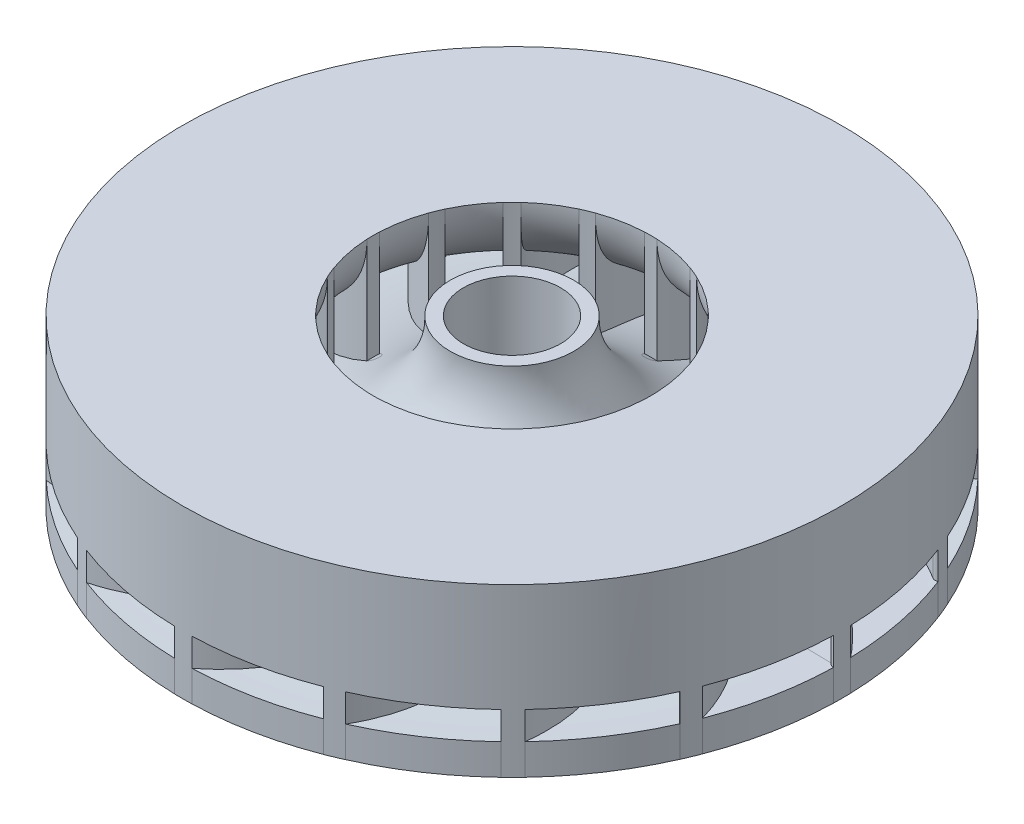
SolidWorks part; units mm, degrees
other "Markup1"
sketch "Sketch14" plane through (34.9924, 18.1689, 34.9924) normal (0.4024, 0.9092, 0.107) x (-0.9091, 0.4106, -0.0699)
material "AA356.0-F"
ref_plane "Front Plane" through (0, 0, 0) normal (0, 0, 1) x (1, 0, 0)
ref_plane "Top Plane" through (0, 0, 0) normal (0, 1, 0) x (1, 0, 0)
ref_plane "Right Plane" through (0, 0, 0) normal (1, 0, 0) x (0, 0, -1)
curve "Shroud Curve"
curve "Impeller Curve"
curve "Blade Curve"
sketch "Sketch2" plane through (0, 0, 0) normal (0, 0, 1) x (1, 0, 0)
  line L0 (14.2896, 17.1821) -> (33.9139, 17.1821)
  line L1 (33.9139, 17.1821) -> (33.9139, 6.0439)
  spline S0 degree 3 poles (-985.6672, 25.6238) (17.121, 24.6036) (14.2699, 20.8626) (14.29, 17.0771) (14.2924, 16.9214) (14.3025, 16.6646) (14.3304, 16.2921) (14.3832, 15.869) (14.4663, 15.4189) (14.5673, 15.0013) (14.692, 14.5874) (14.8412, 14.1777) (15.0158, 13.7731) (15.2158, 13.374) (15.4419, 12.981) (15.6996, 12.5875) (15.9902, 12.1947) (16.3155, 11.8043) (16.6762, 11.4178) (17.0667, 11.0427) (17.4864, 10.6798) (17.9347, 10.329) (18.4109, 9.9911) (18.9142, 9.6665) (19.4435, 9.3553) (20.0062, 9.0533) (20.6105, 8.7577) (21.2468, 8.4745) (21.9134, 8.2045) (22.6083, 7.9485) (23.3475, 7.7013) (24.1283, 7.4655) (24.9558, 7.241) (25.8242, 7.0305) (26.7261, 6.8369) (27.6431, 6.6639) (28.555, 6.5139) (29.435, 6.3888) (30.2578, 6.2886) (30.995, 6.2121) (31.6335, 6.1561) (32.1708, 6.1163) (32.6141, 6.0889) (32.9737, 6.0705) (33.2588, 6.0586) (33.476, 6.0514) (33.6399, 6.0473) (33.7596, 6.0451) (33.8432, 6.0441) (33.8894, 6.0439) (35.7046, 6.0419) (37.504, 6.9456) (38.7227, -993.9019) knots -0.448256 -0.448256 -0.448256 -0.448256 0.001273 0.002543 0.008858 0.020084 0.03357 0.053959 0.071547 0.088816 0.10582 0.123722 0.141437 0.159019 0.177608 0.196155 0.215799 0.236589 0.257482 0.279621 0.301942 0.324462 0.348334 0.372436 0.39676 0.422462 0.44954 0.477978 0.506547 0.536376 0.567388 0.600661 0.634851 0.670917 0.708547 0.746233 0.783584 0.820144 0.853551 0.883668 0.909634 0.93095 0.948727 0.963266 0.974429 0.983176 0.989512 0.994228 0.997631 0.999605 0.999804 1.216827 1.216827 1.216827 1.216827 only from (14.2896, 17.1821) to (33.9139, 6.0439) construction
  spline S1 degree 3 poles (14.2896, 17.1821) (14.2896, 17.1715) (14.2896, 17.1505) (14.29, 17.0771) (14.2924, 16.9214) (14.3025, 16.6646) (14.3304, 16.2921) (14.3832, 15.869) (14.4663, 15.4189) (14.5673, 15.0013) (14.692, 14.5874) (14.8412, 14.1777) (15.0158, 13.7731) (15.2158, 13.374) (15.4419, 12.981) (15.6996, 12.5875) (15.9902, 12.1947) (16.3155, 11.8043) (16.6762, 11.4178) (17.0667, 11.0427) (17.4864, 10.6798) (17.9347, 10.329) (18.4109, 9.9911) (18.9142, 9.6665) (19.4435, 9.3553) (20.0062, 9.0533) (20.6105, 8.7577) (21.2468, 8.4745) (21.9134, 8.2045) (22.6083, 7.9485) (23.3475, 7.7013) (24.1283, 7.4655) (24.9558, 7.241) (25.8242, 7.0305) (26.7261, 6.8369) (27.6431, 6.6639) (28.555, 6.5139) (29.435, 6.3888) (30.2578, 6.2886) (30.995, 6.2121) (31.6335, 6.1561) (32.1708, 6.1163) (32.6141, 6.0889) (32.9737, 6.0705) (33.2588, 6.0586) (33.476, 6.0514) (33.6399, 6.0473) (33.7596, 6.0451) (33.8432, 6.0441) (33.8894, 6.0439) (33.909, 6.0439) (33.9123, 6.0439) (33.9139, 6.0439) knots 0 0 0 0 0.001273 0.002543 0.008858 0.020084 0.03357 0.053959 0.071547 0.088816 0.10582 0.123722 0.141437 0.159019 0.177608 0.196155 0.215799 0.236589 0.257482 0.279621 0.301942 0.324462 0.348334 0.372436 0.39676 0.422462 0.44954 0.477978 0.506547 0.536376 0.567388 0.600661 0.634851 0.670917 0.708547 0.746233 0.783584 0.820144 0.853551 0.883668 0.909634 0.93095 0.948727 0.963266 0.974429 0.983176 0.989512 0.994228 0.997631 0.999605 0.999804 1 1 1 1
ref_axis "Axis1" through (0, 16.8793, 0) along (0, -1, 0)
revolve "Shroud" add sketch "Sketch2" angle 360 about axis through (0, 16.8793, 0) along (0, -1, 0)
sketch "Sketch3" plane through (0, 0, 0) normal (0, 0, 1) x (1, 0, 0)
  line L0 (33.9128, 3.175) -> (33.9128, 0)
  line L1 (33.9128, 0) -> (0, 0)
  line L2 (0, 0) -> (0, 17.1821)
  line L3 (33.9139, 17.1821) -> (-33.9139, 17.1821) construction
  line L4 (6.35, 17.1685) -> (0, 17.1821)
  spline S7 degree 3 poles (-1991.3665, 109.7009) (15.6852, 23.4896) (6.4344, 20.476) (6.3459, 17.0645) (6.3444, 17.0058) (6.3434, 16.947) (6.3404, 16.6729) (6.3533, 16.2816) (6.4048, 15.7563) (6.4711, 15.3126) (6.5686, 14.836) (6.6969, 14.3482) (6.8639, 13.8337) (7.066, 13.3147) (7.3118, 12.7771) (7.594, 12.2427) (7.9215, 11.699) (8.2837, 11.1664) (8.6895, 10.6336) (9.137, 10.1057) (9.6369, 9.5753) (10.1877, 9.0493) (10.7869, 8.5341) (11.4314, 8.0351) (12.1178, 7.5568) (12.8306, 7.1101) (13.5662, 6.695) (14.3337, 6.3043) (15.1445, 5.9339) (15.9967, 5.5857) (16.8758, 5.2653) (17.7806, 4.9716) (18.7099, 4.7037) (19.6624, 4.4606) (20.6367, 4.2412) (21.6306, 4.0447) (22.6521, 3.8684) (23.7077, 3.711) (24.8016, 3.5721) (25.9239, 3.4532) (27.0714, 3.3541) (28.244, 3.275) (29.4928, 3.2133) (30.6331, 3.1786) (31.5843, 3.1645) (32.226, 3.1616) (32.6964, 3.1629) (33.0402, 3.1656) (33.303, 3.1684) (33.5124, 3.1709) (33.6836, 3.173) (33.8026, 3.1742) (33.8663, 3.1747) (33.8858, 3.1748) (33.8929, 3.1749) (33.8999, 3.1749) (35.0826, 3.1853) (36.2737, -0.1737) (31.0149, 2002.8901) knots -0.294083 -0.294083 -0.294083 -0.294083 0.001321 0.003038 0.004754 0.006471 0.008186 0.028756 0.040733 0.054397 0.068031 0.083322 0.098551 0.115379 0.132085 0.150292 0.168289 0.187646 0.206684 0.226919 0.24823 0.270495 0.293593 0.317412 0.341854 0.366841 0.391061 0.415809 0.442244 0.46911 0.496416 0.524176 0.552404 0.581103 0.610263 0.639854 0.669822 0.701044 0.733318 0.766378 0.799876 0.834181 0.869306 0.90937 0.934086 0.952614 0.965565 0.975289 0.982722 0.988577 0.993635 0.99771 0.999002 0.999211 0.999418 0.999624 0.999828 1.102994 1.102994 1.102994 1.102994 only from (6.35, 17.1685) to (33.9128, 3.175) construction
  spline S8 degree 3 poles (6.35, 17.1685) (6.3492, 17.1535) (6.3474, 17.1188) (6.3459, 17.0645) (6.3444, 17.0058) (6.3434, 16.947) (6.3404, 16.6729) (6.3533, 16.2816) (6.4048, 15.7563) (6.4711, 15.3126) (6.5686, 14.836) (6.6969, 14.3482) (6.8639, 13.8337) (7.066, 13.3147) (7.3118, 12.7771) (7.594, 12.2427) (7.9215, 11.699) (8.2837, 11.1664) (8.6895, 10.6336) (9.137, 10.1057) (9.6369, 9.5753) (10.1877, 9.0493) (10.7869, 8.5341) (11.4314, 8.0351) (12.1178, 7.5568) (12.8306, 7.1101) (13.5662, 6.695) (14.3337, 6.3043) (15.1445, 5.9339) (15.9967, 5.5857) (16.8758, 5.2653) (17.7806, 4.9716) (18.7099, 4.7037) (19.6624, 4.4606) (20.6367, 4.2412) (21.6306, 4.0447) (22.6521, 3.8684) (23.7077, 3.711) (24.8016, 3.5721) (25.9239, 3.4532) (27.0714, 3.3541) (28.244, 3.275) (29.4928, 3.2133) (30.6331, 3.1786) (31.5843, 3.1645) (32.226, 3.1616) (32.6964, 3.1629) (33.0402, 3.1656) (33.303, 3.1684) (33.5124, 3.1709) (33.6836, 3.173) (33.8026, 3.1742) (33.8663, 3.1747) (33.8858, 3.1748) (33.8929, 3.1749) (33.8999, 3.1749) (33.9066, 3.175) (33.9109, 3.175) (33.9128, 3.175) knots 0 0 0 0 0.001321 0.003038 0.004754 0.006471 0.008186 0.028756 0.040733 0.054397 0.068031 0.083322 0.098551 0.115379 0.132085 0.150292 0.168289 0.187646 0.206684 0.226919 0.24823 0.270495 0.293593 0.317412 0.341854 0.366841 0.391061 0.415809 0.442244 0.46911 0.496416 0.524176 0.552404 0.581103 0.610263 0.639854 0.669822 0.701044 0.733318 0.766378 0.799876 0.834181 0.869306 0.90937 0.934086 0.952614 0.965565 0.975289 0.982722 0.988577 0.993635 0.99771 0.999002 0.999211 0.999418 0.999624 0.999828 1 1 1 1
revolve "Impeller" add sketch "Sketch3" angle 360 about axis through (0, 16.8793, 0) along (0, -1, 0)
sketch "Sketch6" plane through (0, 0, 0) normal (0, 1, 0) x (1, 0, 0)
  arc A1 (14.2692, -0.6474) -> (14.31, 0.6474) centre (14.2896, 0) cw
  arc A2 (30.638, -13.2667) -> (31.9028, -12.987) centre (31.2704, -13.1269) ccw
  arc A4 (31.013, -13.7212) -> (31.6811, -12.0991) centre (0, 0) ccw
  circle A6 centre (0, 0) radius 33.9128 construction
  arc A9 (15.0709, 0.613) -> (15.0678, -0.6846) centre (0, 0) cw
  circle A12 centre (0, 0) radius 14.2896 construction
  circle A13 centre (0, 0) radius 14.2896 construction
  spline S0 degree 3 poles (29.1527, 999.8802) (2.6027, -2.0333) (8.5201, 0.1935) (14.47, -0.006) (14.7444, -0.017) (15.2838, -0.047) (16.0195, -0.1066) (16.8994, -0.2107) (17.8059, -0.3553) (18.6971, -0.537) (19.5715, -0.7574) (20.405, -1.0093) (21.1987, -1.2906) (21.9628, -1.6029) (22.697, -1.9455) (23.401, -2.3173) (24.074, -2.7162) (24.7234, -3.1458) (25.3546, -3.6107) (25.9646, -4.11) (26.5566, -4.6475) (27.132, -5.2274) (27.7008, -5.8649) (28.2624, -6.5684) (28.8239, -7.3613) (29.3515, -8.2108) (29.8101, -9.0583) (30.1771, -9.8308) (30.4638, -10.5106) (30.6902, -11.1112) (30.8707, -11.644) (31.0313, -12.1706) (31.1418, -12.5811) (31.2149, -12.8827) (31.2453, -13.0144) (31.2619, -13.0887) (31.2681, -13.1165) (31.8566, -15.7731) (31.8137, -18.5676) (1009.2473, 194.9709) knots -0.749934 -0.749934 -0.749934 -0.749934 0.001801 0.003598 0.017879 0.037227 0.073264 0.113069 0.151484 0.191631 0.230352 0.267746 0.303909 0.33893 0.374178 0.408369 0.44158 0.475057 0.508762 0.542655 0.576689 0.611857 0.647988 0.686837 0.727913 0.773243 0.815755 0.852134 0.88353 0.910883 0.93491 0.95607 0.981881 0.989727 0.996094 0.999315 0.999546 0.999774 1.350254 1.350254 1.350254 1.350254 only from (14.2896, 0) to (31.2704, -13.1269) construction
  spline S1 degree 3 poles (14.2896, 0) (14.3035, -0.0004) (14.3453, -0.0018) (14.4701, -0.006) (14.7311, -0.0166) (15.2304, -0.0435) (15.9421, -0.0994) (16.7994, -0.1973) (17.6976, -0.3359) (18.5936, -0.5137) (19.4727, -0.7304) (20.3109, -0.9787) (21.1092, -1.2567) (21.8777, -1.5659) (22.6164, -1.9056) (23.3247, -2.2748) (24.002, -2.6713) (24.6557, -3.0988) (25.2912, -3.5617) (25.9055, -4.0592) (26.5018, -4.5953) (27.0817, -5.1741) (27.65, -5.8051) (28.2122, -6.5022) (28.7719, -7.2835) (29.3068, -8.1341) (29.7723, -8.9839) (30.148, -9.7661) (30.4395, -10.45) (30.6702, -11.0555) (30.8545, -11.5937) (31.0233, -12.1415) (31.1389, -12.5689) (31.2155, -12.8854) (31.2453, -13.0144) (31.2627, -13.0921) (31.2692, -13.1217) (31.2704, -13.1269) knots 0 0 0 0 0.001801 0.005393 0.016104 0.035482 0.069882 0.108171 0.146755 0.187074 0.225954 0.263496 0.299797 0.334945 0.370316 0.40462 0.437936 0.471515 0.505319 0.539308 0.573438 0.608704 0.644938 0.682922 0.724171 0.768833 0.812464 0.849081 0.880722 0.908332 0.932632 0.95409 0.982247 0.989727 0.996094 0.999315 1 1 1 1
  spline S2 degree 1 poles (14.2692, -0.6474) (30.638, -13.2667) knots 0 0 1 1 construction
  spline S3 degree 3 poles (14.2692, -0.6474) (14.4674, -0.6536) (14.8024, -0.6677) (16.6862, -0.7857) (20.2272, -1.376) (25.0147, -3.7201) (28.795, -7.9373) (30.237, -11.4541) (30.638, -13.2667) knots 0 0 0 0 0.026426 0.044044 0.25 0.5 0.75 1 1 1 1
  spline S4 degree 1 poles (14.31, 0.6474) (31.9028, -12.987) knots 0 0 1 1 construction
  spline S5 degree 3 poles (14.31, 0.6474) (14.5007, 0.6414) (14.8171, 0.6283) (16.8017, 0.5101) (20.5738, -0.1052) (25.8167, -2.6593) (29.6637, -6.9585) (31.2206, -10.4525) (31.7637, -12.3924) (31.8537, -12.7652) (31.9028, -12.987) knots 0 0 0 0 0.023975 0.039958 0.25 0.5 0.75 0.952724 0.971634 1 1 1 1
  dimension "D3" = 0.7937
  dimension "D1" = 0.6477
sketch "Sketch5" plane through (0, 0, 0) normal (0, -1, 0) x (1, 0, 0)
  circle A0 centre (0, 0) radius 5
  dimension "D1" = 10
extrude "Shaft Hole" cut sketch "Sketch5" against normal through all
extrude "Blade" add sketch "Sketch6" along normal through all contours S5 A1 A9 S1 A4 | A9 S3 A2 A4 S1 | S3 A2 S5 A1 region at (15.291, 0, 0.3658) region at (25.4108, 0, 3.1183)
pattern_circular "Other Blades" count 16 over 360 about axis through (0, 16.8793, 0) along (0, -1, 0) of "Blade"
sketch "Sketch11" plane through (0, 0, 0) normal (0, 0, 1) x (1, 0, 0)
  line L0 (12.2275, 17.1821) -> (0.9443, 17.1821) construction
  line L5 (-33.9128, 0) -> (33.9128, 0) construction
  line L6 (33.9139, 17.1821) -> (-33.9139, 17.1821) construction
  line L7 (0, 0) -> (0, 17.1821) construction
  line L10 (14.2896, 17.1821) -> (14.2896, 6.3325)
  line L11 (14.2896, 17.1821) -> (6.3507, 17.1821)
  line L12 (14.2896, 17.1821) -> (14.2896, 20.3571)
  line L13 (14.2896, 20.3571) -> (6.3507, 20.3571)
  line L14 (6.3507, 20.3571) -> (6.3507, 17.1821)
  line L17 (-33.9139, 17.1821) -> (-40.2639, 17.1821)
  line L18 (-33.9139, 17.1821) -> (-33.9139, 0)
  line L19 (-33.9139, 0) -> (-40.2639, 0)
  line L20 (-40.2639, 17.1821) -> (-40.2639, 0)
  spline S0 degree 3 poles (-2985.5651, 25.1591) (20.1838, 27.8953) (14.2611, 22.5043) (14.29, 17.0771) (14.2924, 16.9214) (14.3025, 16.6646) (14.3304, 16.2921) (14.3832, 15.869) (14.4663, 15.4189) (14.5673, 15.0013) (14.692, 14.5874) (14.8412, 14.1777) (15.0158, 13.7731) (15.2158, 13.374) (15.4419, 12.981) (15.6996, 12.5875) (15.9902, 12.1947) (16.3155, 11.8043) (16.6762, 11.4178) (17.0667, 11.0427) (17.4864, 10.6798) (17.9347, 10.329) (18.4109, 9.9911) (18.9142, 9.6665) (19.4435, 9.3553) (20.0062, 9.0533) (20.6105, 8.7577) (21.2468, 8.4745) (21.9134, 8.2045) (22.6083, 7.9485) (23.3475, 7.7013) (24.1283, 7.4655) (24.9558, 7.241) (25.8242, 7.0305) (26.7261, 6.8369) (27.6431, 6.6639) (28.555, 6.5139) (29.435, 6.3888) (30.2578, 6.2886) (30.995, 6.2121) (31.6335, 6.1561) (32.1708, 6.1163) (32.6141, 6.0889) (32.9737, 6.0705) (33.2588, 6.0586) (33.476, 6.0514) (33.6399, 6.0473) (33.7596, 6.0451) (33.8432, 6.0441) (33.8894, 6.0439) (36.4987, 6.041) (39.0929, 7.92) (39.9488, -2993.8063) knots -0.646497 -0.646497 -0.646497 -0.646497 0.001273 0.002543 0.008858 0.020084 0.03357 0.053959 0.071547 0.088816 0.10582 0.123722 0.141437 0.159019 0.177608 0.196155 0.215799 0.236589 0.257482 0.279621 0.301942 0.324462 0.348334 0.372436 0.39676 0.422462 0.44954 0.477978 0.506547 0.536376 0.567388 0.600661 0.634851 0.670917 0.708547 0.746233 0.783584 0.820144 0.853551 0.883668 0.909634 0.93095 0.948727 0.963266 0.974429 0.983176 0.989512 0.994228 0.997631 0.999605 0.999804 1.31272 1.31272 1.31272 1.31272 only from (14.2896, 17.1821) to (33.9139, 6.0439) construction
  spline S1 degree 3 poles (-2990.435, 152.3937) (18.5234, 24.3452) (6.447, 20.9618) (6.3459, 17.0645) (6.3444, 17.0058) (6.3434, 16.947) (6.3404, 16.6729) (6.3533, 16.2816) (6.4048, 15.7563) (6.4711, 15.3126) (6.5686, 14.836) (6.6969, 14.3482) (6.8639, 13.8337) (7.066, 13.3147) (7.3118, 12.7771) (7.594, 12.2427) (7.9215, 11.699) (8.2837, 11.1664) (8.6895, 10.6336) (9.137, 10.1057) (9.6369, 9.5753) (10.1877, 9.0493) (10.7869, 8.5341) (11.4314, 8.0351) (12.1178, 7.5568) (12.8306, 7.1101) (13.5662, 6.695) (14.3337, 6.3043) (15.1445, 5.9339) (15.9967, 5.5857) (16.8758, 5.2653) (17.7806, 4.9716) (18.7099, 4.7037) (19.6624, 4.4606) (20.6367, 4.2412) (21.6306, 4.0447) (22.6521, 3.8684) (23.7077, 3.711) (24.8016, 3.5721) (25.9239, 3.4532) (27.0714, 3.3541) (28.244, 3.275) (29.4928, 3.2133) (30.6331, 3.1786) (31.5843, 3.1645) (32.226, 3.1616) (32.6964, 3.1629) (33.0402, 3.1656) (33.303, 3.1684) (33.5124, 3.1709) (33.6836, 3.173) (33.8026, 3.1742) (33.8663, 3.1747) (33.8858, 3.1748) (33.8929, 3.1749) (33.8999, 3.1749) (35.2527, 3.1868) (36.6174, -1.2123) (28.3129, 3002.5827) knots -0.336641 -0.336641 -0.336641 -0.336641 0.001321 0.003038 0.004754 0.006471 0.008186 0.028756 0.040733 0.054397 0.068031 0.083322 0.098551 0.115379 0.132085 0.150292 0.168289 0.187646 0.206684 0.226919 0.24823 0.270495 0.293593 0.317412 0.341854 0.366841 0.391061 0.415809 0.442244 0.46911 0.496416 0.524176 0.552404 0.581103 0.610263 0.639854 0.669822 0.701044 0.733318 0.766378 0.799876 0.834181 0.869306 0.90937 0.934086 0.952614 0.965565 0.975289 0.982722 0.988577 0.993635 0.99771 0.999002 0.999211 0.999418 0.999624 0.999828 1.117896 1.117896 1.117896 1.117896 only from (6.35, 17.1685) to (33.9128, 3.175) construction
  spline S2 degree 3 poles (14.2896, 17.1821) (14.2896, 17.1715) (14.2896, 17.1505) (14.29, 17.0771) (14.2924, 16.9214) (14.3025, 16.6646) (14.3304, 16.2921) (14.3832, 15.869) (14.4663, 15.4189) (14.5673, 15.0013) (14.692, 14.5874) (14.8412, 14.1777) (15.0158, 13.7731) (15.2158, 13.374) (15.4419, 12.981) (15.6996, 12.5875) (15.9902, 12.1947) (16.3155, 11.8043) (16.6762, 11.4178) (17.0667, 11.0427) (17.4864, 10.6798) (17.9347, 10.329) (18.4109, 9.9911) (18.9142, 9.6665) (19.4435, 9.3553) (20.0062, 9.0533) (20.6105, 8.7577) (21.2468, 8.4745) (21.9134, 8.2045) (22.6083, 7.9485) (23.3475, 7.7013) (24.1283, 7.4655) (24.9558, 7.241) (25.8242, 7.0305) (26.7261, 6.8369) (27.6431, 6.6639) (28.555, 6.5139) (29.435, 6.3888) (30.2578, 6.2886) (30.995, 6.2121) (31.6335, 6.1561) (32.1708, 6.1163) (32.6141, 6.0889) (32.9737, 6.0705) (33.2588, 6.0586) (33.476, 6.0514) (33.6399, 6.0473) (33.7596, 6.0451) (33.8432, 6.0441) (33.8894, 6.0439) (33.909, 6.0439) (33.9123, 6.0439) (33.9139, 6.0439) knots 0 0 0 0 0.001273 0.002543 0.008858 0.020084 0.03357 0.053959 0.071547 0.088816 0.10582 0.123722 0.141437 0.159019 0.177608 0.196155 0.215799 0.236589 0.257482 0.279621 0.301942 0.324462 0.348334 0.372436 0.39676 0.422462 0.44954 0.477978 0.506547 0.536376 0.567388 0.600661 0.634851 0.670917 0.708547 0.746233 0.783584 0.820144 0.853551 0.883668 0.909634 0.93095 0.948727 0.963266 0.974429 0.983176 0.989512 0.994228 0.997631 0.999605 0.999804 1 1 1 1
  spline S3 degree 3 poles (6.3507, 17.1821) (6.3497, 17.1625) (6.3475, 17.1233) (6.3459, 17.0645) (6.3444, 17.0058) (6.3434, 16.947) (6.3404, 16.6729) (6.3533, 16.2816) (6.4048, 15.7563) (6.4711, 15.3126) (6.5686, 14.836) (6.6969, 14.3482) (6.8639, 13.8337) (7.066, 13.3147) (7.3118, 12.7771) (7.594, 12.2427) (7.9215, 11.699) (8.2837, 11.1664) (8.6895, 10.6336) (9.137, 10.1057) (9.6369, 9.5753) (10.1877, 9.0493) (10.7869, 8.5341) (11.4314, 8.0351) (12.1178, 7.5568) (12.8306, 7.1101) (13.5662, 6.695) (14.3337, 6.3043) (15.1445, 5.9339) (15.9967, 5.5857) (16.8758, 5.2653) (17.7806, 4.9716) (18.7099, 4.7037) (19.6624, 4.4606) (20.6367, 4.2412) (21.6306, 4.0447) (22.6521, 3.8684) (23.7077, 3.711) (24.8016, 3.5721) (25.9239, 3.4532) (27.0714, 3.3541) (28.244, 3.275) (29.4928, 3.2133) (30.6331, 3.1786) (31.5843, 3.1645) (32.226, 3.1616) (32.6964, 3.1629) (33.0402, 3.1656) (33.303, 3.1684) (33.5124, 3.1709) (33.6836, 3.173) (33.8026, 3.1742) (33.8663, 3.1747) (33.8858, 3.1748) (33.8929, 3.1749) (33.8999, 3.1749) (33.9066, 3.175) (33.9109, 3.175) (33.9128, 3.175) knots -0.000397 -0.000397 -0.000397 -0.000397 0.001321 0.003038 0.004754 0.006471 0.008186 0.028756 0.040733 0.054397 0.068031 0.083322 0.098551 0.115379 0.132085 0.150292 0.168289 0.187646 0.206684 0.226919 0.24823 0.270495 0.293593 0.317412 0.341854 0.366841 0.391061 0.415809 0.442244 0.46911 0.496416 0.524176 0.552404 0.581103 0.610263 0.639854 0.669822 0.701044 0.733318 0.766378 0.799876 0.834181 0.869306 0.90937 0.934086 0.952614 0.965565 0.975289 0.982722 0.988577 0.993635 0.99771 0.999002 0.999211 0.999418 0.999624 0.999828 1 1 1 1
  dimension "D1" = 6.35
  dimension "D2" = 3.175
revolve "Trimming" cut sketch "Sketch11" angle 360 about L7 region at (11.0166, 12.9517, 0) region at (10.3202, 18.7696, 0) region at (-37.0889, 8.591, 0)
sketch "Sketch13" plane through (0, 0, 0) normal (0, -1, 0) x (1, 0, 0)
  line L0 (-3.7548, 1.52) -> (-6.1452, 1.52)
  line L5 (-6.45, 1.2152) -> (-6.45, -1.2152)
  line L6 (-6.1452, -1.52) -> (-3.7548, -1.52)
  line L7 (-3.45, -1.2152) -> (-3.45, 1.2152)
  line L8 (-6.45, 0) -> (-3.45, 0) construction
  line L9 (-5, 1.52) -> (-5, -1.52) construction
  arc A0 (-6.1452, 1.52) -> (-6.45, 1.2152) centre (-6.1452, 1.2152) ccw
  arc A2 (-6.45, -1.2152) -> (-6.1452, -1.52) centre (-6.1452, -1.2152) ccw
  arc A3 (-3.7548, -1.52) -> (-3.45, -1.2152) centre (-3.7548, -1.2152) ccw
  arc A4 (-3.45, 1.2152) -> (-3.7548, 1.52) centre (-3.7548, 1.2152) ccw
  dimension "D1" = 0.3048
  dimension "D2" = 3.04
  dimension "D3" = 5
  dimension "D4" = 1.45
  dimension "D5" = 3
extrude "Keyway" cut sketch "Sketch13" against normal blind 9
